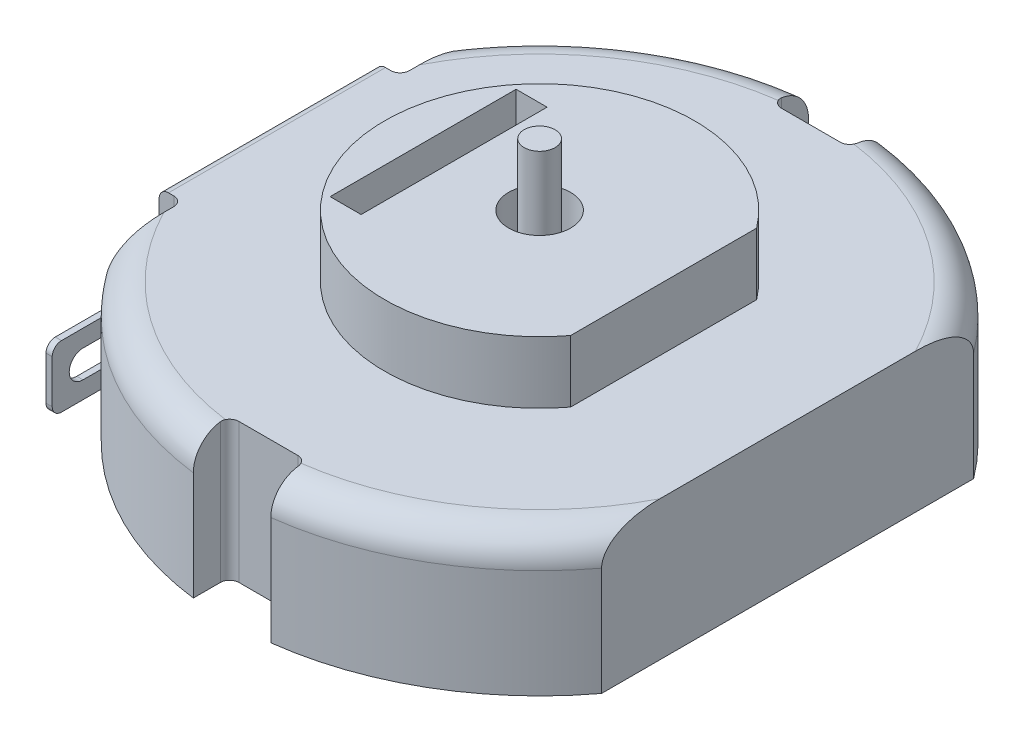
SolidWorks part; units mm, degrees
ref_plane "Front Plane" through (0, 0, 0) normal (0, 0, 1) x (1, 0, 0)
ref_plane "Top Plane" through (0, 0, 0) normal (0, 1, 0) x (1, 0, 0)
ref_plane "Right Plane" through (0, 0, 0) normal (1, 0, 0) x (0, 0, -1)
sketch "Sketch1" plane through (0, 0, 0) normal (0, 1, 0) x (1, 0, 0)
  line L2 (8, -6) -> (8, 6)
  line L4 (-8, -6) -> (-8, 6)
  line L5 (8, -6) -> (-8, 6) construction
  line L6 (8, 6) -> (-8, -6) construction
  arc A0 (-8, -6) -> (8, -6) centre (0, 0) ccw
  arc A1 (8, 6) -> (-8, 6) centre (0, 0) ccw
  dimension "D1" = 20
  dimension "D2" = 16
extrude "Boss-Extrude1" add sketch "Sketch1" along normal blind 4.5
sketch "Sketch2" plane through (0, 4.5, 0) normal (0, 1, 0) x (1, 0, 0)
  line L0 (4, 3) -> (4, -3)
  line L2 (-3.7588, 3) -> (-2.7588, 3)
  line L3 (-3.7588, 3) -> (-3.7588, -3)
  line L4 (-3.7588, -3) -> (-2.7588, -3)
  line L5 (-2.7588, 3) -> (-2.7588, -3)
  arc A0 (4, 3) -> (4, -3) centre (0, 0) ccw
  dimension "D1" = 10
  dimension "D2" = 6
  dimension "D3" = 1
  dimension "D4" = 6
extrude "Boss-Extrude2" add sketch "Sketch2" along normal blind 2
sketch "Sketch3" plane through (0, 6.5, 0) normal (0, 1, 0) x (1, 0, 0)
  circle A0 centre (0, 0) radius 0.5
  circle A1 centre (0, 0) radius 1
  dimension "D1" = 1
  dimension "D2" = 2
extrude "Cut-Extrude1" cut sketch "Sketch3" against normal blind 2
extrude "Boss-Extrude3" add sketch "Sketch3<2>" along normal blind 2 contours A0 region at (0, 6.5, 0)
sketch "Sketch3<2>" plane through (0, 6.5, 0) normal (0, 1, 0) x (1, 0, 0) same geometry as "Sketch3"
sketch "Sketch4" plane through (0, 4.5, 0) normal (0, 1, 0) x (1, 0, 0)
  line L1 (-1.25, -8.75) -> (1.25, -8.75)
  line L2 (-1.25, -8.75) -> (-1.25, -11.25)
  line L3 (-1.25, -11.25) -> (1.25, -11.25)
  line L4 (1.25, -8.75) -> (1.25, -11.25)
  line L5 (-1.25, -8.75) -> (1.25, -11.25) construction
  line L6 (-1.25, -11.25) -> (1.25, -8.75) construction
  arc A0 (-8, -6) -> (8, -6) centre (0, 0) ccw construction
  point P0 (0, -10)
  dimension "D1" = 2.5
  dimension "D2" = 2.5
fillet "Fillet1" radius 1 2 edges at (0, 4.5, -10) (0, 4.5, 10)
extrude "Cut-Extrude2" cut sketch "Sketch4" against normal through all
mirror "Mirror1" about plane through (0, 0, 0) normal (0, 0, 1) of "Cut-Extrude2"
fillet "Fillet2" radius 0.3 4 edges at (-1.25, 2.25, -8.75) (1.25, 2.25, -8.75) (1.25, 2.25, 8.75) (-1.25, 2.25, 8.75)
sketch "Sketch6" plane through (0, 0, 0) normal (0, 0, 1) x (1, 0, 0)
  line L0 (-8, 4.5) -> (-8.4729, 4.5)
  line L1 (-8.7729, 4.2) -> (-8.7729, 3.0289)
  line L2 (-8.7729, 3.0289) -> (-8, 3.0289)
  line L3 (-8, 3.5) -> (-8, 0) construction
  line L4 (-8, 3.0289) -> (-8, 4.5)
  arc A0 (-8.4729, 4.5) -> (-8.7729, 4.2) centre (-8.4729, 4.2) ccw
  dimension "D1" = 0.3
extrude "Boss-Extrude4" add sketch "Sketch6" along normal mid plane 7
fillet "Fillet3" radius 0.3 2 edges at (-8, 3.7645, -3.5) (-8, 3.7645, 3.5)
sketch "Sketch7" plane through (0, 0, 0) normal (0, 0, 1) x (1, 0, 0)
  line L0 (-8, 3.5) -> (-8, 0) construction
  line L1 (-8.7729, 2.6965) -> (-8, 2.6965)
  line L2 (-8.7729, 2.6965) -> (-8.7729, 0)
  line L3 (-8.7729, 0) -> (-8, 0)
  line L4 (-8, 2.6965) -> (-8, 0)
extrude "Boss-Extrude5" add sketch "Sketch7" along normal mid plane 7
sketch "Sketch8" plane through (0, 0, -3.5) normal (0, 0, -1) x (-1, 0, 0)
  line L0 (8, 0) -> (8.7729, 2.6965) construction
  line L2 (8.2237, 2.3465) -> (8.4237, 2.3465)
  line L3 (8.2237, 2.3465) -> (8.2237, 0.3465)
  line L4 (8.2237, 0.3465) -> (8.4237, 0.3465)
  line L5 (8.4237, 2.3465) -> (8.4237, 0.3465)
  line L6 (8, 2.6965) -> (8.7729, 2.6965) construction
  dimension "D1" = 2
  dimension "D2" = 0.2
  dimension "D3" = 0.35
extrude "Boss-Extrude6" add sketch "Sketch8" along normal blind 4
fillet "Fillet4" radius 0.3 2 edges at (-8.3237, 0.3465, -7.5) (-8.3237, 2.3465, -7.5)
sketch "Sketch9" plane through (-8.4237, 0, 0) normal (-1, 0, 0) x (0, 0, 1)
  line L0 (-6.507, 1.3465) -> (-5.0873, 1.3465) construction
  line L1 (-6.507, 1.7902) -> (-5.0873, 1.7902)
  line L2 (-6.507, 0.9029) -> (-5.0873, 0.9029)
  line L3 (-7.5, 0.6465) -> (-7.5, 2.0465) construction
  arc A0 (-6.507, 1.7902) -> (-6.507, 0.9029) centre (-6.507, 1.3465) ccw
  arc A1 (-5.0873, 0.9029) -> (-5.0873, 1.7902) centre (-5.0873, 1.3465) ccw
  point P2 (-5.7971, 1.3465)
  point P11 (-7.5, 1.3465)
extrude "Cut-Extrude3" cut sketch "Sketch9" against normal up to surface (0.2 mm away) up to face at (-8.2237, 1.3465, -6.0874)
mirror "Mirror2" about plane through (0, 0, 0) normal (0, 0, 1) of "Cut-Extrude3", "Fillet4", "Boss-Extrude6"
